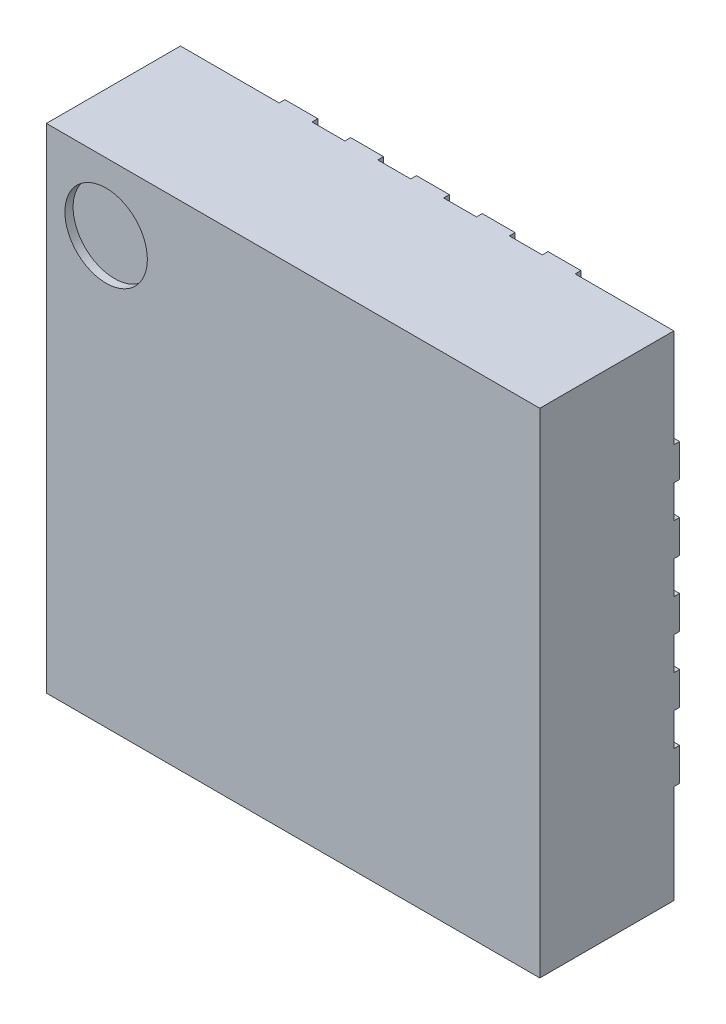
SolidWorks part; units mm, degrees
ref_plane "Front Plane" through (0, 0, 0) normal (0, 0, 1) x (1, 0, 0)
ref_plane "Top Plane" through (0, 0, 0) normal (0, 1, 0) x (1, 0, 0)
ref_plane "Right Plane" through (0, 0, 0) normal (1, 0, 0) x (0, 0, -1)
sketch "Sketch1" plane through (0, 0, 0) normal (0, 0, 1) x (1, 0, 0)
  line L1 (-1.5, -1.5) -> (1.5, -1.5)
  line L2 (-1.5, -1.5) -> (-1.5, 1.5)
  line L3 (-1.5, 1.5) -> (1.5, 1.5)
  line L4 (1.5, -1.5) -> (1.5, 1.5)
  line L5 (0, 1.5) -> (0, -1.5) construction
  line L6 (-1.5, 0) -> (1.5, 0) construction
  point P0 (0, 0)
  dimension "D1" = 3
  dimension "D2" = 3
extrude "Boss-Extrude1" add sketch "Sketch1" along normal blind 0.815 from offset 0.035
sketch "Sketch2" plane through (0, 0, 0.85) normal (0, 0, 1) x (1, 0, 0)
  circle A0 centre (-1.1369, 1.0905) radius 0.2508
extrude "Cut-Extrude3" cut sketch "Sketch2" against normal blind 0.05
sketch "Sketch3" plane through (0, 0, 0.035) normal (0, 0, -1) x (-1, 0, 0)
  line L0 (1.5, 1.5) -> (1.5, -1.5) construction
  line L1 (1.5, 0.9) -> (1.1, 0.9)
  line L2 (1.5, 0.9) -> (1.5, 0.7)
  line L3 (1.5, 0.7) -> (1.1, 0.7)
  line L4 (1.1, 0.9) -> (1.1, 0.7)
  point P6 (1.5, 0.8)
  dimension "D1" = 0.2
  dimension "D2" = 0.4
  dimension "D3" = 0.8
extrude "Boss-Extrude2" add sketch "Sketch3" along normal up to surface (0.035 mm away) up to plane "Front Plane"
pattern_linear "LPattern1" count 5 spacing 0.4 along (0, -1, 0) of "Boss-Extrude2"
sketch "Sketch4" plane through (0, 0, 0) normal (0, 0, -1) x (-1, 0, 0)
  line L0 (1.2022, 0.9) -> (1.1, 0.8)
  line L1 (1.1, 0.9) -> (1.5, 0.9) construction
  line L2 (1.1, 0.7) -> (1.1, 0.9) construction
  line L3 (1.1, 0.8) -> (1.1, 0.9)
  line L4 (1.1, 0.9) -> (1.2022, 0.9)
  point P6 (1.1, 0.8)
extrude "Cut-Extrude4" cut sketch "Sketch4" against normal up to surface (0.035 mm away) up to face at (-1.0833, 0, 0.035)
mirror "Mirror1" about plane through (0, 0, 0) normal (0, 1, 0) of "Cut-Extrude4"
ref_axis "Axis1" through (0, 0, -0.0425) along (0, 0, 1)
pattern_circular "CirPattern1" count 4 over 360 about axis through (0, 0, -0.0425) along (0, 0, 1) of "Cut-Extrude4", "LPattern1", "Boss-Extrude2"
sketch "Sketch5" plane through (0, 0, 0.035) normal (0, 0, -1) x (-1, 0, 0)
  line L0 (0.5136, 0.85) -> (0.85, 0.5136)
  line L1 (-0.85, -0.85) -> (0.85, -0.85)
  line L2 (-0.85, -0.85) -> (-0.85, 0.85)
  line L3 (-0.85, 0.85) -> (0.85, 0.85) construction
  line L4 (0.85, -0.85) -> (0.85, 0.85) construction
  line L5 (0, 0.85) -> (0, -0.85) construction
  line L6 (-0.85, 0) -> (0.85, 0) construction
  line L7 (-0.85, 0.85) -> (0.5136, 0.85)
  line L8 (0.85, 0.5136) -> (0.85, -0.85)
  point P0 (0, 0)
  dimension "D1" = 1.7
  dimension "D2" = 1.7
  dimension "D3" = 45
extrude "Boss-Extrude3" add sketch "Sketch5" along normal up to surface (0.035 mm away) up to face at (0.8, 1.2804, 0)
